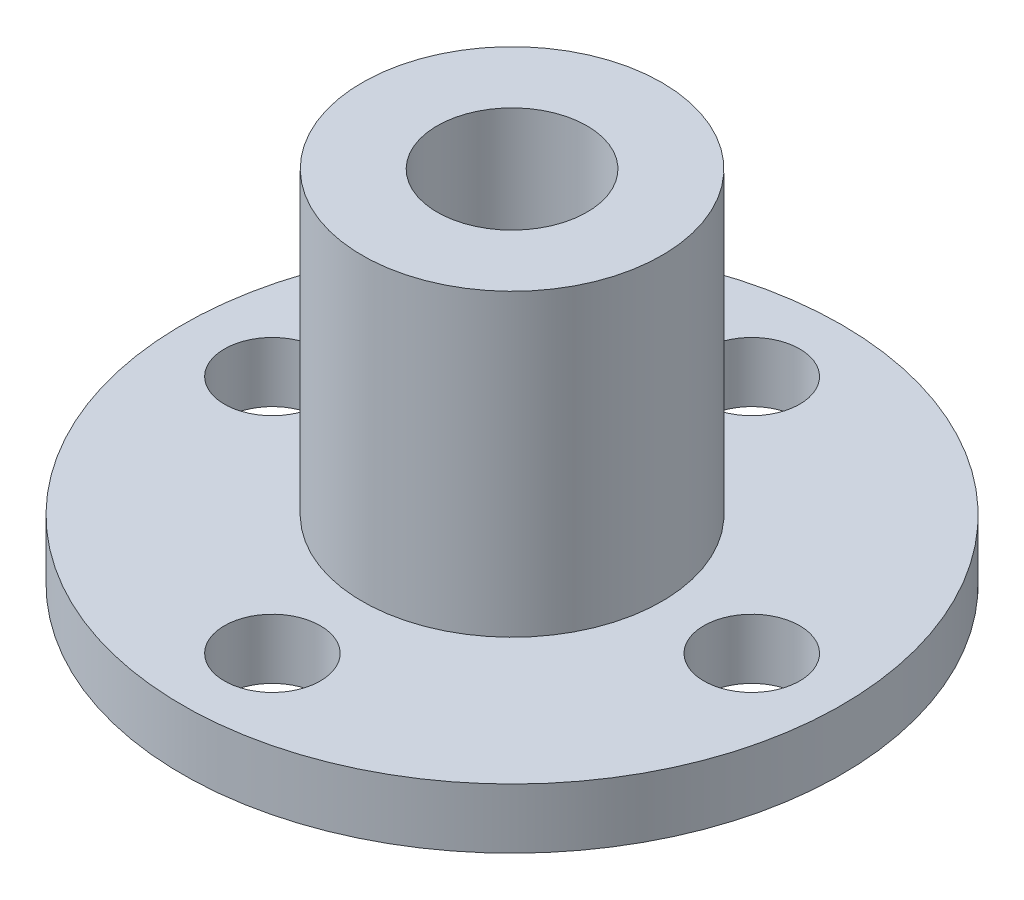
SolidWorks part; units mm, degrees
ref_plane "前视基准面" through (0, 0, 0) normal (0, 0, 1) x (1, 0, 0)
ref_plane "上视基准面" through (0, 0, 0) normal (0, 1, 0) x (1, 0, 0)
ref_plane "右视基准面" through (0, 0, 0) normal (1, 0, 0) x (0, 0, -1)
sketch "草图1" plane through (0, 0, 0) normal (0, 0, 1) x (1, 0, 0)
  line L0 (-2.5, 0.014) -> (-11, 0.014)
  line L1 (-11, 0.014) -> (-11, 2.014)
  line L2 (-11, 2.014) -> (-5, 2.014)
  line L3 (-5, 2.014) -> (-5, 12.014)
  line L4 (-5, 12.014) -> (-2.5, 12.014)
  line L5 (-2.5, 12.014) -> (-2.5, 0.014)
  line L6 (0, 0) -> (0, 12.028) construction
  dimension "D1" = 5
  dimension "D2" = 10
  dimension "D3" = 2
  dimension "D4" = 10
  dimension "D5" = 22
revolve "旋转1" add sketch "草图1" angle 360 about L6
sketch "草图2" plane through (0, 0.014, 0) normal (0, -1, 0) x (1, 0, 0)
  circle A0 centre (-8, 0) radius 1.6
  circle A1 centre (0, 0) radius 2.5 construction
  circle A2 centre (0, 8) radius 1.6
  circle A3 centre (8, 0) radius 1.6
  circle A4 centre (0, -8) radius 1.6
  point P4 (0, 0)
  point P15 (0, 0)
  dimension "D1" = 3.2
  dimension "D2" = 8
  dimension "D3" = 4
extrude "切除-拉伸1" cut sketch "草图2" against normal blind 10
ref_axis "基准轴1" through (0, 12.014, 0) along (0, -1, 0)
